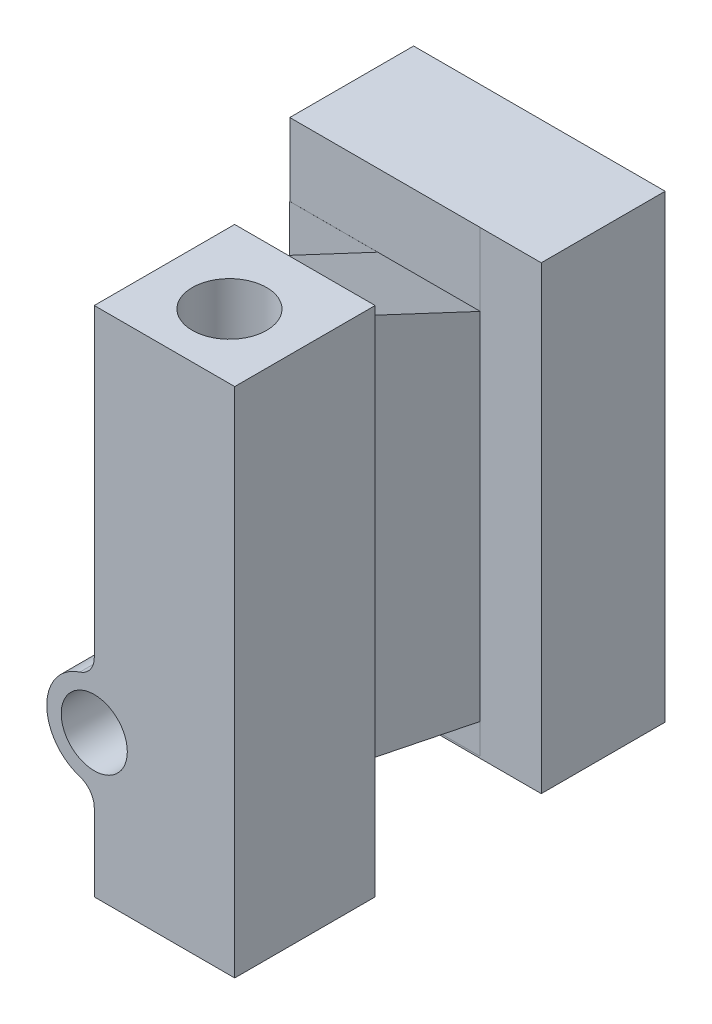
SolidWorks part; units mm, degrees
ref_plane "Front Plane" through (0, 0, 0) normal (0, 0, 1) x (1, 0, 0)
ref_plane "Top Plane" through (0, 0, 0) normal (0, 1, 0) x (1, 0, 0)
ref_plane "Right Plane" through (0, 0, 0) normal (1, 0, 0) x (0, 0, -1)
sketch "Sketch1" plane through (0, 0, 0) normal (0, 0, 1) x (1, 0, 0)
  line L1 (-22.1812, 49.3094) -> (11.8188, 49.3094)
  line L2 (-22.1812, 49.3094) -> (-22.1812, -74.6906)
  line L3 (-22.1812, -74.6906) -> (11.8188, -74.6906)
  line L4 (11.8188, 49.3094) -> (11.8188, -74.6906)
  dimension "D1" = 124
  dimension "D2" = 34
extrude "Boss-Extrude1" add sketch "Sketch1" along normal blind 34
sketch "Sketch2" plane through (0, 0, 34) normal (0, 0, 1) x (1, 0, 0)
  line L0 (-22.1812, 49.3094) -> (-22.1812, -74.6906) construction
  circle A0 centre (-22.1812, -40.2508) radius 11.504
extrude "Boss-Extrude2" add sketch "Sketch2" against normal blind 34
fillet "Fillet1" radius 5 2 edges at (-22.1812, -51.7548, 17) (-22.1812, -28.7468, 17)
sketch "Sketch3" plane through (0, -74.6906, 0) normal (0, -1, 0) x (1, 0, 0)
  circle A0 centre (-4.8936, 17.1062) radius 13.5862
extrude "Cut-Extrude1" cut sketch "Sketch3" against normal blind 50
sketch "Sketch4" plane through (0, 0, 34) normal (0, 0, 1) x (1, 0, 0)
  circle A0 centre (-22.1812, -40.2508) radius 8
  arc A1 (-25.6665, -29.2874) -> (-25.6665, -51.2142) centre (-22.1812, -40.2508) ccw construction
extrude "Cut-Extrude2" cut sketch "Sketch4" against normal blind 20
sketch "Sketch5" plane through (0, 0, 0) normal (0, 0, -1) x (-1, 0, 0)
  line L1 (-7.2618, 48.6909) -> (17.5691, 48.6909)
  line L2 (-7.2618, 48.6909) -> (-7.2618, -62.513)
  line L3 (-7.2618, -62.513) -> (17.5691, -62.513)
  line L4 (17.5691, 48.6909) -> (17.5691, -62.513)
extrude "Boss-Extrude3" add sketch "Sketch5" along normal blind 30
sketch "Sketch6" plane through (0, 0, -30) normal (0, 0, -1) x (-1, 0, 0)
  line L1 (-22.0319, 48.3699) -> (38.868, 48.3699)
  line L2 (-22.0319, 48.3699) -> (-22.0319, -62.9411)
  line L3 (-22.0319, -62.9411) -> (38.868, -62.9411)
  line L4 (38.868, 48.3699) -> (38.868, -62.9411)
extrude "Boss-Extrude4" add sketch "Sketch6" along normal blind 30
sketch "Sketch7" plane through (0, 49.3094, 0) normal (0, 1, 0) x (1, 0, 0)
  circle A0 centre (-5.0915, -18.3589) radius 8.9987
extrude "Cut-Extrude3" cut sketch "Sketch7" against normal blind 100
sketch "Sketch9" plane through (7.2618, 0, 0) normal (1, 0, 0) x (0, 0, -1)
  line L0 (-0.0119, 53.1584) -> (-0.0119, 44.8625)
  line L1 (-0.0119, 44.8625) -> (30.0187, 30.7835)
  line L2 (30.0187, 30.7835) -> (30.0187, 53.1584)
  line L3 (30.0187, 53.1584) -> (-0.0119, 53.1584)
  line L4 (-0.0119, -49.0284) -> (-0.0119, -66.3738)
  line L5 (-0.0119, -66.3738) -> (29.9948, -69.2814)
  line L6 (29.9948, -69.2814) -> (29.9948, -55.1732)
  line L7 (29.9948, -55.1732) -> (-0.0119, -49.0284)
extrude "Cut-Extrude5" cut sketch "Sketch9" against normal blind 100
sketch "Sketch10" plane through (-38.868, 0, 0) normal (-1, 0, 0) x (0, 0, 1)
  circle A0 centre (-47.9821, -43.6836) radius 8.225
extrude "Cut-Extrude6" cut sketch "Sketch10" against normal blind 10
